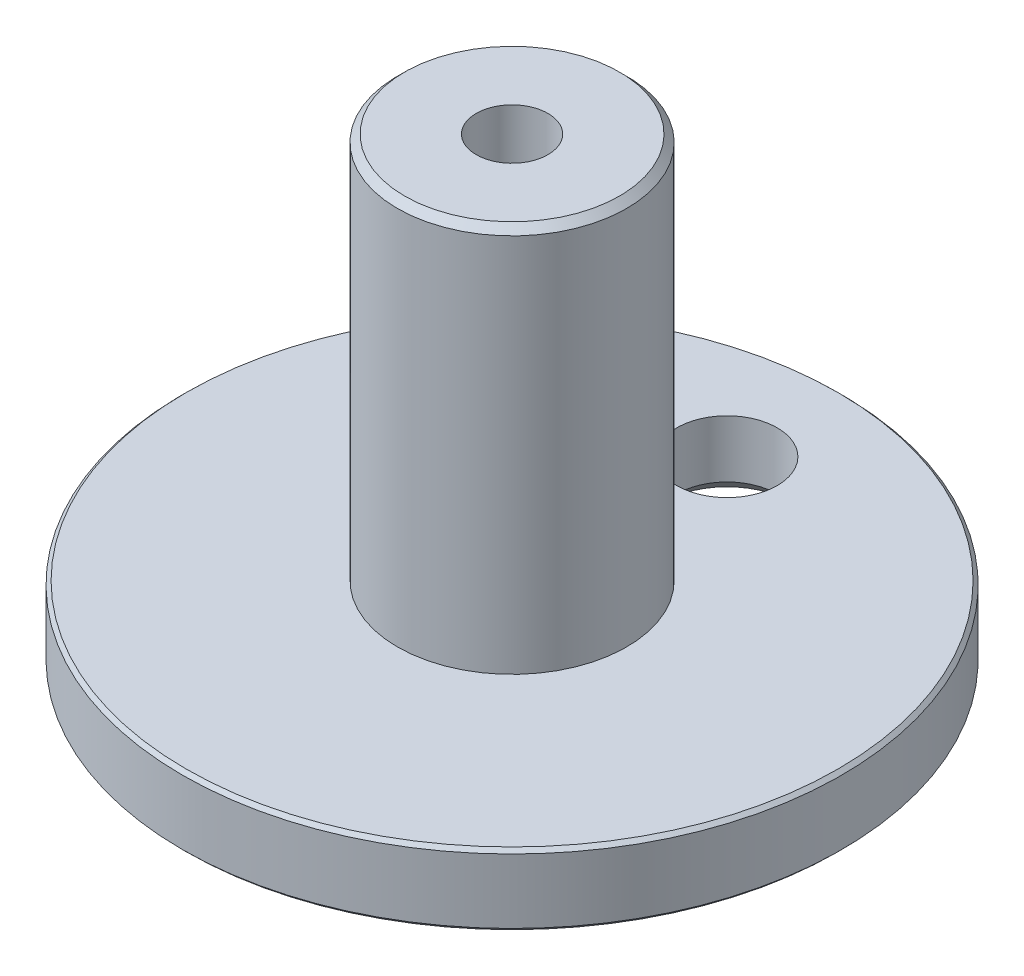
SolidWorks part; units mm, degrees
ref_plane "Front Plane" through (0, 0, 0) normal (0, 0, 1) x (1, 0, 0)
ref_plane "Top Plane" through (0, 0, 0) normal (0, 1, 0) x (1, 0, 0)
ref_plane "Right Plane" through (0, 0, 0) normal (1, 0, 0) x (0, 0, -1)
sketch "Sketch1" plane through (0, 0, 0) normal (0, 1, 0) x (1, 0, 0)
  circle A0 centre (0, 0) radius 23
  circle A1 centre (0, 0) radius 8
  circle A2 centre (0, 0) radius 2.5
  circle A3 centre (0, 15) radius 3.5
  point P7 (0, 0)
  point P8 (0, 14.9673)
  dimension "D1" = 46
  dimension "D2" = 16
  dimension "D3" = 5
  dimension "D4" = 7
  dimension "D5" = 15
extrude "Boss-Extrude1" add sketch "Sketch1" along normal blind 5 contours A0 A3 A1 | A1 A2 region at (-22.3495, 0, 0) region at (-7.7737, 0, 0)
extrude "Boss-Extrude2" add sketch "Sketch1<3>" along normal blind 32 contours A1 A2 region at (-7.7737, 0, 0)
sketch "Sketch1<3>" plane through (0, 0, 0) normal (0, 1, 0) x (1, 0, 0) same geometry as "Sketch1"
chamfer "Chamfer1" distance 0.5 angle 45 1 edges at (0, 32, 8)
chamfer "Chamfer2" distance 0.25 angle 45 2 edges at (0, 0, 23) (0, 5, 23)
chamfer "Chamfer3" distance 1 angle 45 1 edges at (0, 0, -11.5)
